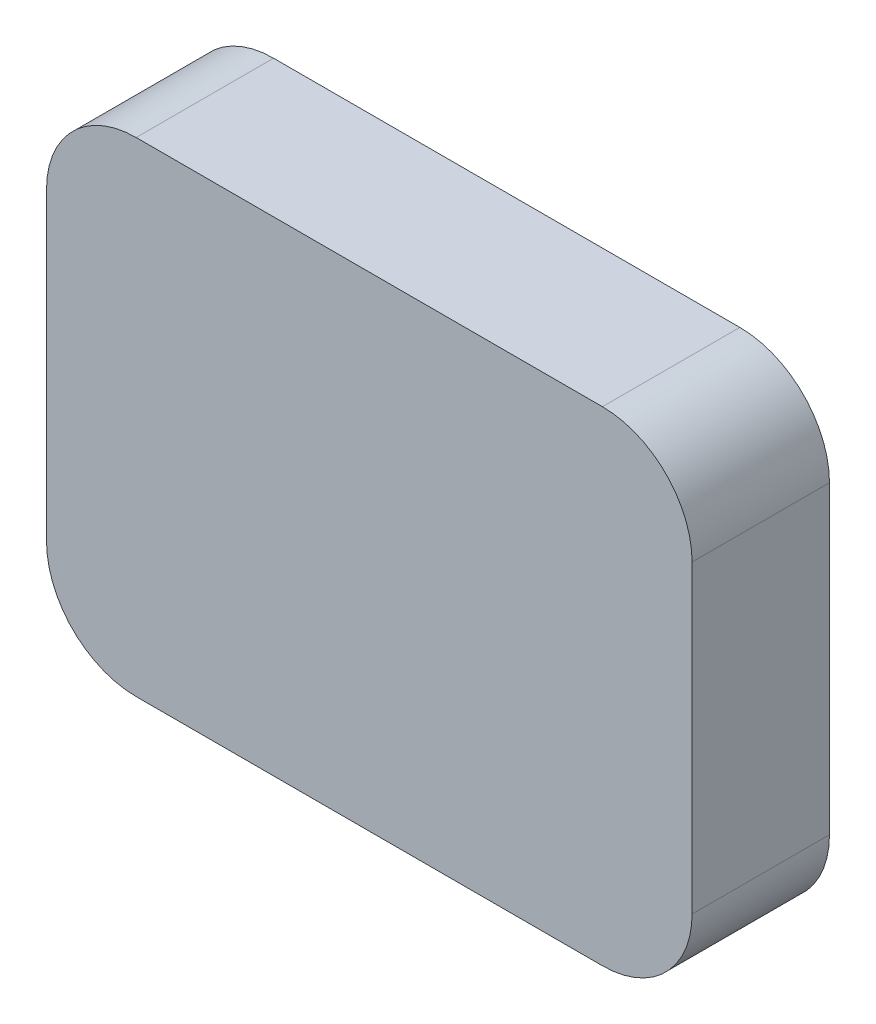
SolidWorks part; units mm, degrees
ref_plane "Plan de face" through (0, 0, 0) normal (0, 0, 1) x (1, 0, 0)
ref_plane "Plan de dessus" through (0, 0, 0) normal (0, 1, 0) x (1, 0, 0)
ref_plane "Plan de droite" through (0, 0, 0) normal (1, 0, 0) x (0, 0, -1)
sketch "Esquisse1" plane through (0, 0, 0) normal (0, 0, 1) x (1, 0, 0)
  line L1 (-26, 27) -> (26, 27)
  line L2 (-36, 17) -> (-36, -17)
  line L3 (-26, -27) -> (26, -27)
  line L4 (36, 17) -> (36, -17)
  line L5 (-36, 27) -> (36, -27) construction
  line L6 (-36, -27) -> (36, 27) construction
  arc A0 (-36, -17) -> (-26, -27) centre (-26, -17) ccw
  arc A1 (26, -27) -> (36, -17) centre (26, -17) ccw
  arc A2 (26, 27) -> (36, 17) centre (26, 17) cw
  arc A3 (-26, 27) -> (-36, 17) centre (-26, 17) ccw
  point P0 (0, 0)
  dimension "D1" = 10
  dimension "D2" = 52
  dimension "D3" = 34
sketch "profil" plane through (0, 0, 0) normal (1, 0, 0) x (0, 0, -1)
  line L0 (0, -24.9) -> (4.1391, -24.9)
  line L1 (4.1391, -24.9) -> (14.1228, -20.8)
  line L3 (14.1228, -27) -> (0, -27)
  line L4 (0, -27) -> (0, -24.9)
  line L6 (0, -17) -> (0, -27) construction
  line L7 (0, -27) -> (0, 27) construction
  line L8 (14.1228, -20.8) -> (14.1228, -22.9)
  line L9 (14.1228, -24.9) -> (14.1228, -27)
  line L10 (14.1228, -20.8) -> (14.1228, -27) construction
  arc A1 (14.1228, -22.9) -> (14.1228, -24.9) centre (14.1228, -23.9) cw
  dimension "D1" = 2
  dimension "D3" = 14.1228
  dimension "D4" = 6.2
sweep "Balayage1" add profiles "profil" path "Esquisse1"
extrude "Boss.-Extru.1" add sketch "Esquisse1<3>" along normal blind 1.2
sketch "Esquisse1<3>" plane through (0, 0, 0) normal (0, 0, 1) x (1, 0, 0) same geometry as "Esquisse1"
fillet "Congé1" radius 2 9 edges at (-31.5861, 22.5861, 0) (-33.9, 0, 0) (-31.5861, -22.5861, 0) (-13, -24.9, 0) (13, -24.9, 0) (31.5861, -22.5861, 0) (33.9, 0, 0) (31.5861, 22.5861, 0) (0, 24.9, 0)
equation "\"buse\"=0.4"
equation "\"coque\"= \"buse\" * 4"
equation "\"diam_silicone\"=2"
equation "\"D1@profil\" = \"diam_silicone\""
equation "\"couche\"=0.2"
equation "\"D1@Boss.-Extru.1\"=\"fond\""
equation "\"fond\"= \"couche\" * 6"
equation "\"D2@Esquisse1\"=\"dim_ext_L@boitier_balaye-1.Part\""
equation "\"D3@profil\"=\"hauteur_boitier@boitier_balaye-1.Part\""
equation "\"D4@profil\"=\"epaisseur_jonction@boitier_balaye-1.Part\""
equation "\"D3@Esquisse1\"=\"dim_ext@boitier_balaye-1.Part\""
